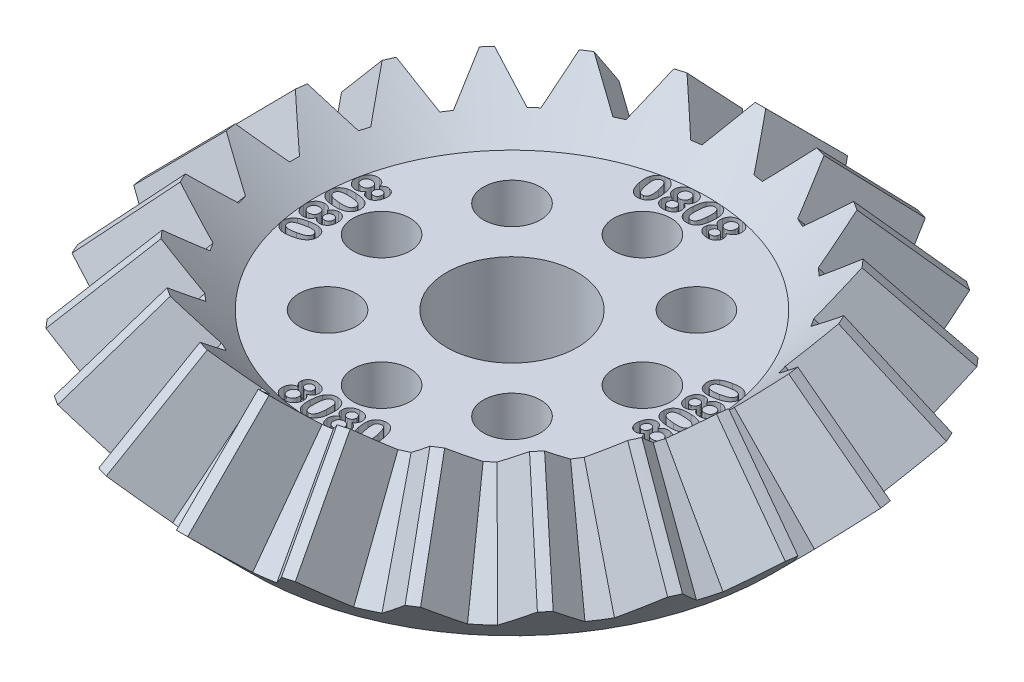
SolidWorks part; units mm, degrees
ref_plane "Front Plane" through (0, 0, 0) normal (0, 0, 1) x (1, 0, 0)
ref_plane "Top Plane" through (0, 0, 0) normal (0, 1, 0) x (1, 0, 0)
ref_plane "Right Plane" through (0, 0, 0) normal (1, 0, 0) x (0, 0, -1)
sketch "Sketch2" plane through (0, 0, 0) normal (0, 0, 1) x (1, 0, 0)
  line L6 (0, 0) -> (0, 6)
  line L7 (0, 0) -> (-16, 0)
  line L8 (0, 6) -> (-12, 6)
  line L9 (-16, 0) -> (-20.2426, 4.2426)
  line L14 (-20.2426, 4.2426) -> (-15.2426, 9.2426)
  line L15 (-12, 6) -> (-15.2426, 9.2426)
  dimension "D1" = 6
  dimension "D2" = 16
  dimension "D3" = 12
  dimension "D4" = 45
  dimension "D5" = 6
revolve "Revolve4" add sketch "Sketch2" angle 360 about L6
sketch "Sketch3" plane through (0, 0, 0) normal (0, 0, 1) x (1, 0, 0)
  line L0 (0, 0) -> (0, 24.4853) construction
  line L1 (0, 24.4853) -> (0, -16.6359) construction
  line L2 (0, 24.4853) -> (-24.6315, -0.1462) construction
  line L3 (-15.2426, 9.2426) -> (-20.2426, 4.2426) construction
ref_plane "Plane1" through (-8, -8, 0) normal (-0.7071, -0.7071, 0) x (0, 0, 1)
sketch "Sketch4" plane through (-8, -8, 0) normal (-0.7071, -0.7071, 0) x (0, 0, 1)
  line L0 (0, 9.4379) -> (0, 20.6725) construction
  line L1 (0, 0) -> (0, 17.3137) construction
  line L4 (0.6553, 14.0042) -> (3, 17.9558)
  line L5 (0.6553, 14.0042) -> (-0.6553, 14.0042)
  line L6 (-3, 17.9558) -> (3, 17.9558)
  line L7 (-0.6553, 14.0042) -> (-3, 17.9558)
  point P11 (0, 14.0042)
  point P13 (0, 17.9558)
  point P14 (0, 14.0042)
  point P15 (0, 17.9558)
  dimension "D1" = 3
sketch "Sketch5" plane through (0, 6, 0) normal (0, 1, 0) x (1, 0, 0)
  line L0 (0, 0) -> (0, -8)
  circle A0 centre (0, 0) radius 4
  circle A1 centre (0, -8) radius 1.75
  dimension "D1" = 8
  dimension "D3" = 3.5
  dimension "D2" = 8
extrude "Cut-Extrude3" cut sketch "Sketch5" against normal blind 10 contours A0 region at (-2.7484, 6, -2.7484)
extrude "Cut-Extrude4" cut sketch "Sketch5<3>" against normal blind 10 contours A1
sketch "Sketch5<3>" plane through (0, 6, 0) normal (0, 1, 0) x (1, 0, 0) same geometry as "Sketch5"
pattern_circular "CirPattern3" count 8 over 360 about axis through (0, 0, 0) along (0, 1, 0) of "Cut-Extrude4"
extrude "Cut-Extrude9" cut sketch "Sketch4" against normal blind 10 draft 5 contours L4 L6 L7 L5
pattern_circular "CirPattern9" count 22 over 360 about axis through (0, 0, 0) along (0, 1, 0) of "Cut-Extrude9" reverse direction yes
sketch "Sketch6" plane through (0, 6, 0) normal (0, 1, 0) x (1, 0, 0)
  text T0 "8080" font "Arial Rounded MT Bold" height 2
extrude "Cut-Extrude10" cut sketch "Sketch6" against normal blind 1
pattern_circular "CirPattern10" count 4 over 360 about axis through (0, 0, 0) along (0, 1, 0) of "Cut-Extrude10" reverse direction yes
